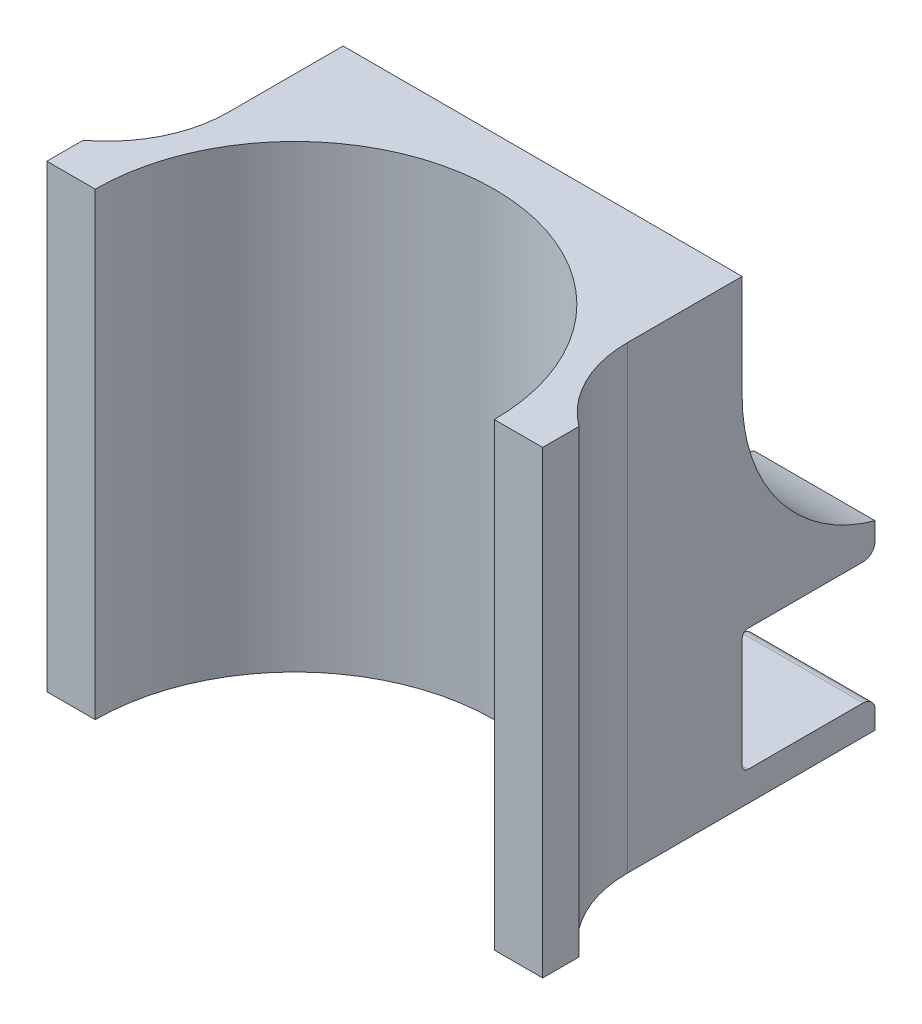
SolidWorks part; units mm, degrees
ref_plane "Front Plane" through (0, 0, 0) normal (0, 0, 1) x (1, 0, 0)
ref_plane "Top Plane" through (0, 0, 0) normal (0, 1, 0) x (1, 0, 0)
ref_plane "Right Plane" through (0, 0, 0) normal (1, 0, 0) x (0, 0, -1)
sketch "Sketch1" plane through (0, 0, 0) normal (0, 1, 0) x (1, 0, 0)
  line L1 (-33, 41) -> (33, 41)
  line L2 (-33, 41) -> (-33, -50.041)
  line L3 (-33, -50.041) -> (33, -50.041)
  line L4 (33, 41) -> (33, -50.041)
  line L5 (-41, 6) -> (41, 6)
  line L6 (-41, 6) -> (-41, 0)
  line L7 (-41, 0) -> (41, 0)
  line L8 (41, 6) -> (41, 0)
  line L9 (-33, 41) -> (-13, 41)
  line L10 (-33, 41) -> (-33, 63)
  line L11 (-33, 63) -> (-13, 63)
  line L12 (-13, 41) -> (-13, 63)
  line L13 (33, 41) -> (13, 41)
  line L14 (33, 41) -> (33, 63)
  line L15 (33, 63) -> (13, 63)
  line L16 (13, 41) -> (13, 63)
  circle A0 centre (0, 0) radius 33
  dimension "D1" = 66
  dimension "D2" = 22
  dimension "D3" = 35
  dimension "D4" = 6
  dimension "D5" = 8
  dimension "D6" = 20
  dimension "D7" = 20
extrude "Boss-Extrude1" add sketch "Sketch1" along normal blind 30 contours A0 L5 L4 L1 L2 | L6 L7 L2 L5 | A0 L5 L2 | L8 L5 L4 L7 | A0 L4 L5 | L1 L12 L11 L10 | L14 L15 L16 L13 region at (-23, 0, -52) region at (-23, 0, -40.2529) region at (-32.8352, 0, -4.5025) region at (-37, 0, -3) region at (32.8352, 0, -4.5025) region at (37, 0, -3)
sketch "Sketch2" plane through (0, 0, -63) normal (0, 0, -1) x (-1, 0, 0)
  line L0 (-33, 30) -> (-33, 0) construction
  line L1 (-33, 25.1) -> (33, 25.1)
  line L2 (-33, 25.1) -> (-33, 4.9)
  line L3 (-33, 4.9) -> (33, 4.9)
  line L4 (33, 25.1) -> (33, 4.9)
  line L5 (33, 30) -> (33, 0) construction
  point P6 (-33, 15)
  point P7 (-33, 15)
  dimension "D1" = 20.2
extrude "Cut-Extrude1" cut sketch "Sketch2" against normal up to surface (22 mm away) up to face at (0, 15, -41)
sketch "Sketch3" plane through (0, 30, 0) normal (0, 1, 0) x (1, 0, 0)
  line L1 (-41, 6) -> (41, 6)
  line L2 (-41, 6) -> (-41, 0)
  line L3 (-41, 0) -> (41, 0)
  line L4 (41, 6) -> (41, 0)
  line L5 (33, 6) -> (41, 6) construction
  line L6 (-41, 6) -> (-41, 0) construction
  line L7 (-33, 63) -> (-33, 6) construction
  line L8 (-33, 41) -> (33, 41)
  line L9 (-33, 41) -> (-33, 0)
  line L10 (-33, 0) -> (33, 0)
  line L11 (33, 41) -> (33, 0)
  line L12 (-13, 41) -> (13, 41) construction
  circle A0 centre (0, 0) radius 33
  arc A1 (33, 0) -> (-33, 0) centre (0, 0) ccw construction
  arc M10 (-33, 0) -> (33, 0) centre (0, 0) cw
  line M11 (33, 0) -> (41, 0)
  line M12 (41, 0) -> (41, 6)
  line M13 (41, 6) -> (33, 6)
  line M14 (33, 6) -> (33, 63)
  line M17 (13, 41) -> (-13, 41)
  line M20 (-33, 63) -> (-33, 6)
  line M21 (-33, 6) -> (-41, 6)
  line M22 (-41, 6) -> (-41, 0)
  line M23 (-41, 0) -> (-33, 0)
extrude "Boss-Extrude2" add sketch "Sketch3" along normal blind 46 contours L8 L1 M20 M10 M14 M17 | L11 M13 M11 M12 | L9 M21 M22 M23 | L1 L9 M10 | L11 L1 M10 region at (-37, 30, -3) region at (-32.2529, 30, -23.5) region at (-32.8352, 30, -4.5025) region at (32.8352, 30, -4.5025) region at (37, 30, -3)
fillet "Fillet1" radius 30 2 edges at (-23, 30, -41) (23, 30, -41)
fillet "Fillet2" radius 20 2 edges at (33, 38, -6) (-33, 38, -6)
fillet "Fillet3" radius 10 4 edges at (13, 42.0068, -41) (-13, 42.0068, -41) (-13, 2.45, -41) (13, 2.45, -41)
fillet "Fillet4" radius 2 4 edges at (23, 25.1, -63) (23, 4.9, -63) (-23, 25.1, -63) (-23, 4.9, -63)
fillet "Fillet5" radius 1 4 edges at (-18, 25.1, -41) (18, 25.1, -41) (18, 4.9, -41) (-18, 4.9, -41)
